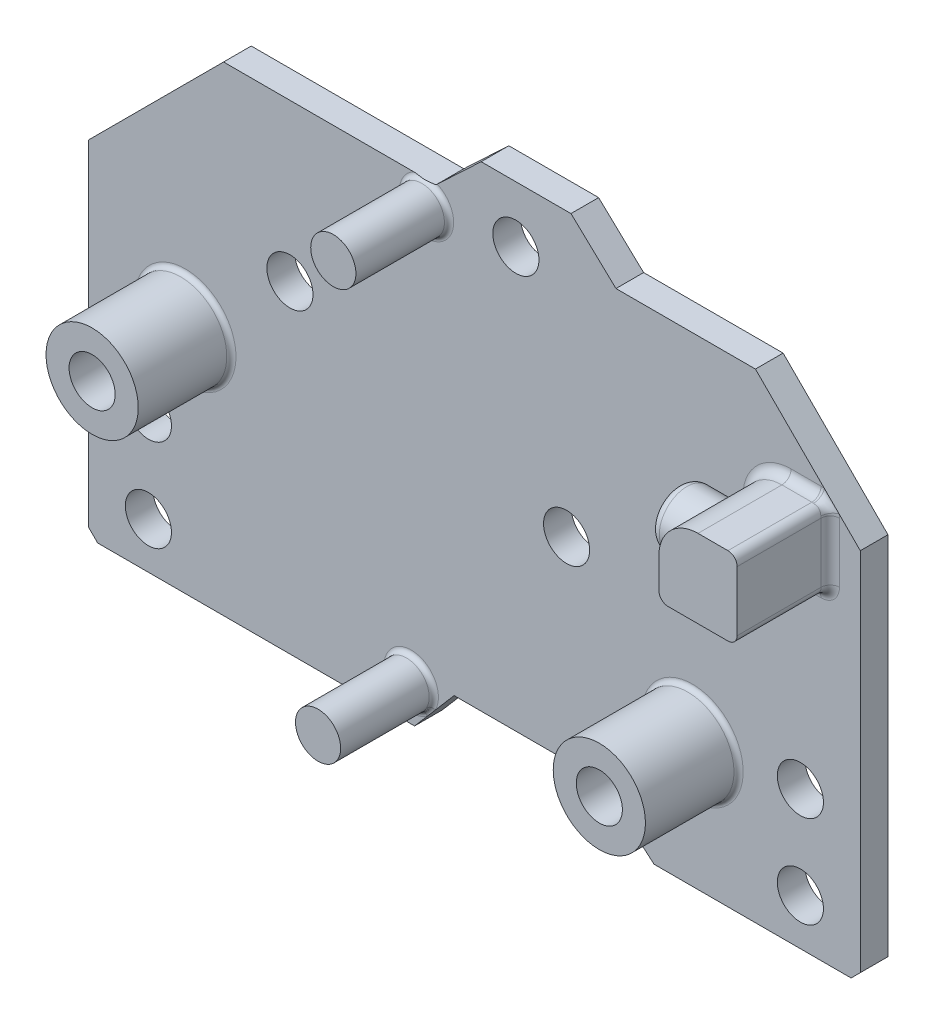
SolidWorks part; units mm, degrees
ref_plane "정면" through (0, 0, 0) normal (0, 0, 1) x (1, 0, 0)
ref_plane "윗면" through (0, 0, 0) normal (0, 1, 0) x (1, 0, 0)
ref_plane "우측면" through (0, 0, 0) normal (1, 0, 0) x (0, 0, -1)
sketch "스케치1" plane through (0, 0, 0) normal (0, 0, 1) x (1, 0, 0)
  line L0 (-6.4864, -27.5) -> (-2.1959, -22.5)
  line L1 (0.7354, 29.1) -> (10.4737, 29.1)
  line L2 (-41.8494, 9.8477) -> (-41.8494, -27.5)
  line L3 (-41.8494, -27.5) -> (-6.4864, -27.5)
  line L4 (41.8494, 13.1286) -> (41.8494, -27.5)
  line L5 (-2.1959, -22.5) -> (13.658, -22.5)
  line L6 (13.658, -22.5) -> (19.4848, -27.5)
  line L7 (19.4848, -27.5) -> (41.8494, -27.5)
  line L8 (-27.1972, 24.5) -> (-41.8494, 9.8477)
  line L9 (30.478, 24.5) -> (41.8494, 13.1286)
  line L10 (0.7354, 29.1) -> (-4.1444, 24.5)
  line L11 (-4.1444, 24.5) -> (-27.1972, 24.5)
  line L12 (10.4737, 29.1) -> (15.3535, 24.5)
  line L13 (15.3535, 24.5) -> (30.478, 24.5)
  circle A0 centre (-20, 7.5) radius 2.5
  circle A1 centre (4.5, 23) radius 2.5
  circle A2 centre (10, -1.5) radius 2.5
  point P0 (0, 0)
  dimension "D3" = 5
  dimension "D6" = 5
  dimension "D7" = 5
  dimension "D4" = 5
  dimension "D2" = 52
  dimension "D5" = 9
  dimension "D8" = 24.5
  dimension "D9" = 15.5
  dimension "D10" = 24.5
  dimension "D11" = 30
  dimension "D12" = 4.6
extrude "보스-돌출1" add sketch "스케치1" along normal blind 3
sketch "스케치2" plane through (0, 0, 3) normal (0, 0, 1) x (1, 0, 0)
  line L0 (-41.8494, 9.8477) -> (-41.8494, -27.5) construction
  line L1 (-41.8494, -27.5) -> (-6.4864, -27.5) construction
  line L2 (41.8494, -27.5) -> (41.8494, 13.1286) construction
  line L3 (19.4848, -27.5) -> (41.8494, -27.5) construction
  line L4 (-41.8494, -27.5) -> (-6.4864, -27.5) construction
  line L5 (-4.1444, 24.5) -> (-27.1972, 24.5) construction
  line L6 (-41.8494, 9.8477) -> (-41.8494, -27.5) construction
  circle A0 centre (-31.3494, -2.5) radius 2.5
  circle A1 centre (-31.3494, -2.5) radius 5
  circle A2 centre (23.6494, -14) radius 5
  circle A3 centre (23.6494, -14) radius 2.5
  circle A4 centre (-5.1972, 21.9) radius 2.45
  circle A5 centre (-6.8494, -23.5) radius 2.45
  dimension "D1" = 10
  dimension "D2" = 5
  dimension "D5" = 10
  dimension "D6" = 5
  dimension "D9" = 4.9
  dimension "D12" = 4.9
  dimension "D3" = 10.5
  dimension "D4" = 25
  dimension "D7" = 18.2
  dimension "D8" = 13.5
  dimension "D10" = 2.6
  dimension "D11" = 22
  dimension "D13" = 4
  dimension "D14" = 35
extrude "보스-돌출3" add sketch "스케치2" along normal blind 10.1
extrude "컷-돌출1" cut sketch "스케치2<2>" against normal up to next contours A0 | A3
sketch "스케치2<2>" plane through (0, 0, 3) normal (0, 0, 1) x (1, 0, 0) same geometry as "스케치2"
fillet "필렛1" radius 0.5 4 edges at (18.6494, -14, 3) (-7.6472, 21.9, 3) (-36.3494, -2.5, 3) (-9.2994, -23.5, 3)
sketch "스케치3" plane through (0, 0, 3) normal (0, 0, 1) x (1, 0, 0)
  line L0 (31.105, 7.5675) -> (37.5938, 7.5675)
  line L1 (38.5938, 8.5675) -> (38.5938, 15.0563)
  line L2 (37.5938, 16.0563) -> (34.3494, 16.0563)
  line L3 (30.105, 8.5675) -> (30.105, 11.8119)
  line L4 (41.8494, -27.5) -> (41.8494, 13.1286) construction
  line L6 (19.4848, -27.5) -> (41.8494, -27.5) construction
  arc A0 (34.3494, 16.0563) -> (30.105, 11.8119) centre (34.3494, 11.8119) ccw
  arc A1 (31.105, 7.5675) -> (30.105, 8.5675) centre (31.105, 8.5675) cw
  arc A2 (37.5938, 7.5675) -> (38.5938, 8.5675) centre (37.5938, 8.5675) ccw
  arc A3 (38.5938, 15.0563) -> (37.5938, 16.0563) centre (37.5938, 15.0563) ccw
  dimension "D3" = 1
  dimension "D1" = 7.5
  dimension "D2" = 39.3119
extrude "보스-돌출4" add sketch "스케치3" along normal blind 10.1 contours A0 L3 A1 L0 A2 L1 A3 L2
sketch "스케치4" plane through (30.105, 0, 0) normal (-1, 0, 0) x (0, 0, 1)
  line L0 (13.1, 11.8119) -> (3, 11.8119) construction
  circle A0 centre (8.05, 11.8119) radius 3
  dimension "D1" = 6
extrude "보스-돌출5" add sketch "스케치4" along normal mid plane 6
fillet "필렛2" radius 1 1 edges at (27.105, 11.8119, 11.05)
fillet "필렛4" radius 1 8 edges at (35.9716, 16.0563, 3) (38.5938, 11.8119, 3) (34.3494, 7.5675, 3) (30.105, 10.1897, 3) (31.3482, 14.8131, 3) (38.3009, 15.7634, 3) (38.3009, 7.8604, 3) (30.3979, 7.8604, 3)
sketch "스케치5" plane through (0, 0, 3) normal (0, 0, 1) x (1, 0, 0)
  line L1 (-41.8494, -27.5) -> (-29.3494, -27.5)
  line L2 (-41.8494, -27.5) -> (-41.8494, -8)
  line L3 (-41.8494, -8) -> (-29.3494, -8)
  line L4 (-29.3494, -27.5) -> (-29.3494, -8)
  line L5 (41.8494, -27.5) -> (29.3494, -27.5)
  line L6 (41.8494, -27.5) -> (41.8494, -8)
  line L7 (41.8494, -8) -> (29.3494, -8)
  line L8 (29.3494, -27.5) -> (29.3494, -8)
  circle A0 centre (-35.3494, -12.5) radius 2.5
  circle A1 centre (-35.3494, -22.5) radius 2.5
  circle A2 centre (35.3494, -12.5) radius 2.5
  circle A3 centre (35.3494, -22.5) radius 2.5
  dimension "D5" = 5
  dimension "D6" = 5
  dimension "D7" = 5
  dimension "D8" = 5
  dimension "D1" = 19.5
  dimension "D2" = 19.5
  dimension "D3" = 12.5
  dimension "D4" = 12.5
  dimension "D9" = 10
  dimension "D10" = 10
  dimension "D11" = 5
  dimension "D12" = 5
extrude "컷-돌출2" cut sketch "스케치5" against normal blind 10 contours A0 | A1 | A3 | A2 region at (-35.3494, -12.5, 3) region at (-35.3494, -22.5, 3) region at (35.3494, -22.5, 3)
chamfer "모따기1" distance 1 angle 45 2 edges at (41.8494, -27.5, 1.5) (-41.8494, -27.5, 1.5)
